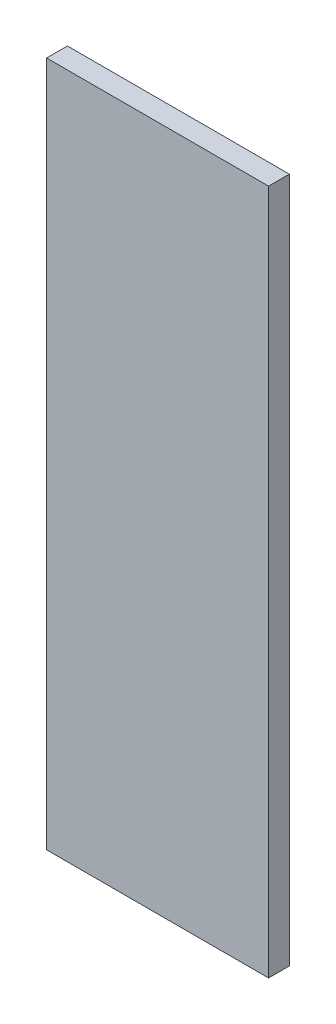
SolidWorks part; units mm, degrees
ref_plane "Front Plane" through (0, 0, 0) normal (0, 0, 1) x (1, 0, 0)
ref_plane "Top Plane" through (0, 0, 0) normal (0, 1, 0) x (1, 0, 0)
ref_plane "Right Plane" through (0, 0, 0) normal (1, 0, 0) x (0, 0, -1)
sketch "Sketch1" plane through (0, 0, 0) normal (0, 0, 1) x (1, 0, 0)
  line L1 (-16.0087, 29.2306) -> (187.1913, 29.2306)
  line L2 (-16.0087, 29.2306) -> (-16.0087, -598.6574)
  line L3 (-16.0087, -598.6574) -> (187.1913, -598.6574)
  line L4 (187.1913, 29.2306) -> (187.1913, -598.6574)
  line L5 (-16.0087, 29.2306) -> (187.1913, -598.6574) construction
  line L6 (-16.0087, -598.6574) -> (187.1913, 29.2306) construction
  point P0 (85.5913, -284.7134)
  dimension "D1" = 627.888
  dimension "D2" = 203.2
extrude "Boss-Extrude1" add sketch "Sketch1" along normal blind 19.05 contours L2 L1 L4 L3
